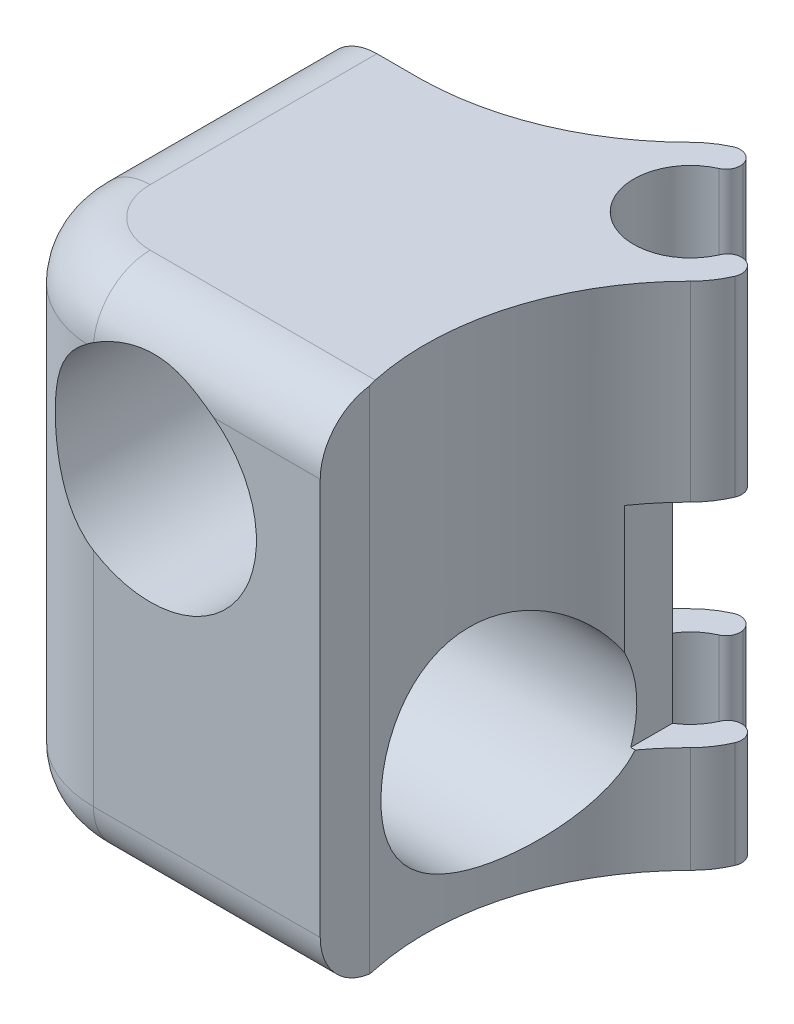
SolidWorks part; units mm, degrees
material "ABS"
ref_plane "Front Plane" through (0, 0, 0) normal (0, 0, 1) x (1, 0, 0)
ref_plane "Top Plane" through (0, 0, 0) normal (0, 1, 0) x (1, 0, 0)
ref_plane "Right Plane" through (0, 0, 0) normal (1, 0, 0) x (0, 0, -1)
sketch "Sketch1" plane through (0, 0, 0) normal (0, 1, 0) x (1, 0, 0)
  line L0 (17.1185, 8.9948) -> (8.6333, 17.4801) construction
  line L1 (12.1662, -12.1662) -> (-11.8338, -12.1662)
  line L2 (12.1662, -12.1662) -> (12.1662, -8.6881)
  line L3 (-4.7533, 11.8338) -> (-11.8338, 11.8338)
  line L4 (-11.8338, -12.1662) -> (-11.8338, 11.8338)
  line L5 (12.1662, -12.1662) -> (-11.8338, 11.8338) construction
  line L6 (12.8759, 13.2375) -> (-11.8338, -12.1662) construction
  line L7 (12.8759, 13.2375) -> (31.9999, 9.2592) construction
  line L8 (12.8759, 13.2375) -> (8.3528, 33.4646) construction
  line L9 (18.7501, 12.0155) -> (16.7921, 12.4228)
  line L10 (11.5665, 19.0929) -> (12.003, 17.1411)
  arc A0 (12.003, 17.1411) -> (16.7921, 12.4228) centre (12.8759, 13.2375) ccw
  arc A1 (17.1185, 8.9948) -> (18.7501, 12.0155) centre (12.8759, 13.2375) ccw
  arc A2 (17.1185, 8.9948) -> (12.1662, -8.6881) centre (30.3628, -4.2494) ccw
  arc A3 (8.6333, 17.4801) -> (-4.7533, 11.8338) centre (-5.0019, 31.1153) cw
  arc A4 (11.5665, 19.0929) -> (8.6333, 17.4801) centre (12.8759, 13.2375) ccw
  point P0 (0, 0)
  point P10 (12.8759, 13.2375)
  point P11 (12.1662, -8.6881)
  point P12 (-4.7533, 11.8338)
  dimension "D3" = 8
  dimension "D4" = 12
  dimension "D1" = 24
  dimension "D2" = 24
extrude "Boss-Extrude1" add sketch "Sketch1" along normal blind 36
sketch "Sketch2" plane through (-11.8338, 0, 0) normal (-1, 0, 0) x (0, 0, 1)
  line L0 (-11.8338, 0) -> (12.1662, 0) construction
  line L1 (12.1662, 36) -> (12.1662, 0) construction
  circle A0 centre (0.1662, 10) radius 7.5
  dimension "D3" = 15
  dimension "D1" = 10
  dimension "D2" = 12
extrude "Cut-Extrude1" cut sketch "Sketch2" against normal through all
sketch "Sketch3" plane through (0, 0, 12.1662) normal (0, 0, 1) x (1, 0, 0)
  line L0 (-11.8338, 36) -> (12.1662, 36) construction
  line L2 (-11.8338, 36) -> (-11.8338, 0) construction
  circle A0 centre (0.1662, 26) radius 7.5
  dimension "D1" = 15
  dimension "D2" = 10
  dimension "D3" = 12
extrude "Cut-Extrude2" cut sketch "Sketch3" against normal through all
fillet "Fillet1" radius 8 1 edges at (-11.8338, 18, 12.1662)
fillet "Fillet2" radius 4 6 edges at (-11.8338, 0, -3.8338) (-9.4907, 0, 9.823) (4.1662, 36, 12.1662) (-9.4907, 36, 9.823) (4.1662, 0, 12.1662) (-11.8338, 36, -3.8338)
ref_plane "Plane1" through (0, 15, 0) normal (0, 1, 0) x (1, 0, 0)
fillet "Fillet3" radius 1 2 edges at (12.003, 18, -17.1411) (16.7921, 18, -12.4228)
fillet "Fillet4" radius 1 2 edges at (11.5665, 18, -19.0929) (18.7501, 18, -12.0155)
sketch "Sketch4" plane through (0, 15, 0) normal (0, 1, 0) x (1, 0, 0)
  line L0 (15, 0) -> (27.824, 3.6094)
  line L1 (15, -15) -> (-15, -15)
  line L2 (15, -15) -> (15, 15)
  line L3 (15, 15) -> (-15, 15)
  line L4 (-15, -15) -> (-15, 15)
  line L5 (15, -15) -> (-15, 15) construction
  line L6 (15, 15) -> (-15, -15) construction
  line L7 (27.824, 3.6094) -> (23.4248, 30.4022)
  line L8 (23.4248, 30.4022) -> (6.1717, 29.445)
  line L9 (6.1717, 29.445) -> (0, 15)
  point P0 (0, 0)
  dimension "D1" = 30
  dimension "D2" = 30
extrude "Cut-Extrude3" cut sketch "Sketch4" against normal mid plane 15 contours L8 L9 L3 L2 L0 L7 region at (16.1928, 15, -17.4028)
